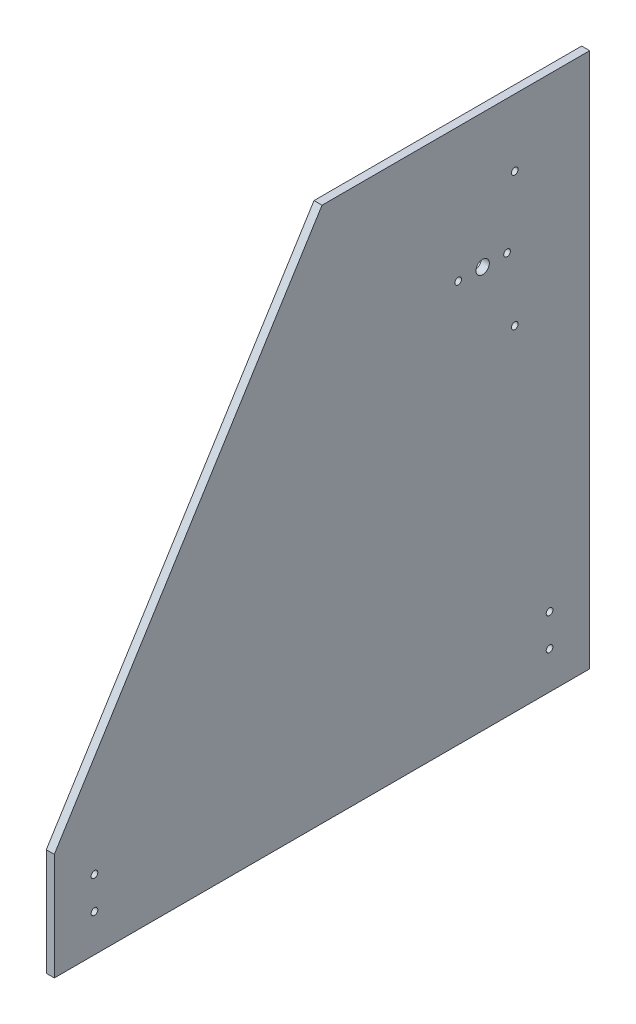
SolidWorks part; units mm, degrees
material "Wrought Stainless Steel"
ref_plane "Front Plane" through (0, 0, 0) normal (0, 0, 1) x (1, 0, 0)
ref_plane "Top Plane" through (0, 0, 0) normal (0, 1, 0) x (1, 0, 0)
ref_plane "Right Plane" through (0, 0, 0) normal (1, 0, 0) x (0, 0, -1)
sketch "Sketch1" plane through (0, 0, 0) normal (1, 0, 0) x (0, 0, -1)
  line L0 (0, -2343.7616) -> (0, 114844.3172) construction
  line L1 (-2343.7616, 0) -> (114844.3172, 0) construction
  line L2 (0, 80) -> (400, 80) construction
  line L3 (0, 0) -> (400, 0)
  line L5 (200, 400) -> (400, 400)
  line L6 (400, 0) -> (400, 400)
  line L7 (0, 80) -> (200, 400)
  line L8 (0, 80) -> (0, 0)
  line L9 (-1000, 40) -> (49000, 40) construction
  line L10 (200, -1000) -> (200, 49000) construction
  line L11 (344, -1000) -> (344, 49000) construction
  line L12 (320, -1008.4066) -> (320, 48991.5934) construction
  line L13 (301.75, 300) -> (338.25, 300) construction
  circle A0 centre (30, 52) radius 2.5
  circle A2 centre (30, 28) radius 2.5
  circle A3 centre (370, 28) radius 2.5
  circle A4 centre (370, 52) radius 2.5
  circle A5 centre (344, 350) radius 2.5
  circle A6 centre (344, 250) radius 2.5
  circle A7 centre (320, 300) radius 5
  circle A8 centre (338.25, 300) radius 2.5
  circle A9 centre (301.75, 300) radius 2.5
  point P14 (0, 40)
  point P21 (200, 0)
  point P38 (320, 300)
  dimension "D7" = 5
  dimension "D9" = 5
  dimension "D14" = 10
  dimension "D16" = 36.5
  dimension "D17" = 5
  dimension "D15" = 5
  dimension "D1" = 400
  dimension "D2" = 400
  dimension "D3" = 80
  dimension "D4" = 200
  dimension "D5" = 30
  dimension "D6" = 56
  dimension "D8" = 12
  dimension "D10" = 50
  dimension "D11" = 100
  dimension "D12" = 80
  dimension "D13" = 50
extrude "Boss-Extrude1" add sketch "Sketch1" along normal blind 6
